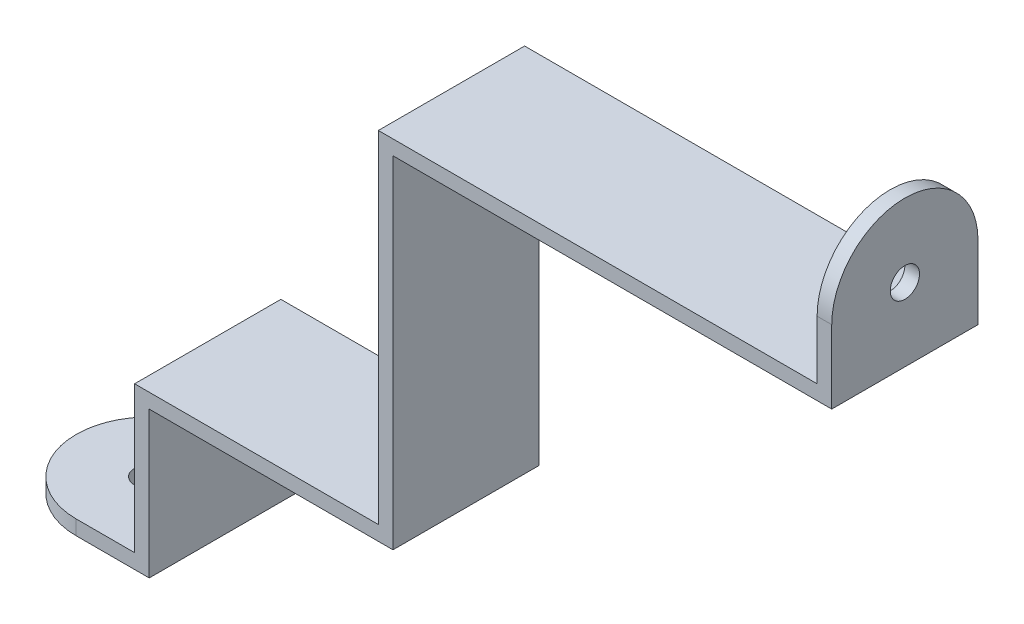
SolidWorks part; units mm, degrees
ref_plane "Front Plane" through (0, 0, 0) normal (0, 0, 1) x (1, 0, 0)
ref_plane "Top Plane" through (0, 0, 0) normal (0, 1, 0) x (1, 0, 0)
ref_plane "Right Plane" through (0, 0, 0) normal (1, 0, 0) x (0, 0, -1)
sketch "Sketch1" plane through (0, 0, 0) normal (0, 0, 1) x (1, 0, 0)
  line L0 (0, 0) -> (0, 35)
  line L3 (-1.5, 36.5) -> (-1.5, 35)
  line L4 (-1.5, 35) -> (-1.5, 1.5)
  line L5 (-1.5, 1.5) -> (-16.5, 1.5)
  line L6 (0, 35) -> (45, 35)
  line L7 (45, 35) -> (45, 50)
  line L8 (45, 50) -> (43.5, 50)
  line L9 (0, 0) -> (-25, 0)
  line L10 (-25, 0) -> (-25, -15)
  line L11 (-25, -15) -> (-40, -15)
  line L12 (-40, -15) -> (-40, -13.5)
  line L13 (-40, -13.5) -> (-26.5, -13.5)
  line L14 (-26.5, -13.5) -> (-26.5, 1.5)
  line L15 (-26.5, 1.5) -> (-16.5, 1.5)
  line L16 (43.5, 50) -> (43.5, 36.5)
  line L17 (43.5, 36.5) -> (-1.5, 36.5)
extrude "Boss-Extrude1" add sketch "Sketch1" along normal blind 15
sketch "Sketch5" plane through (43.5, 0, 0) normal (-1, 0, 0) x (0, 0, 1)
  line L0 (7.5, 50) -> (7.5, 42.5) construction
  line L1 (15, 50) -> (0, 50) construction
  line L2 (0, 42.5) -> (0, 50)
  line L3 (0, 50) -> (15, 50)
  line L4 (15, 50) -> (15, 42.5)
  circle A0 centre (7.5, 42.5) radius 1.5
  arc A1 (15, 42.5) -> (0, 42.5) centre (7.5, 42.5) ccw
  line M1 (0, 50) -> (0, 36.5)
  line M3 (15, 36.5) -> (15, 50)
  line M4 (15, 50) -> (0, 50)
extrude "Cut-Extrude3" cut sketch "Sketch5" against normal blind 10 contours A0 | A1 L3 M1 | A1 M3 M4 region at (43.5, 48.3247, 13.3247) region at (43.5, 48.3247, 1.6753) region at (43.5, 42.5, 7.5)
sketch "Sketch6" plane through (0, -13.5, 0) normal (0, 1, 0) x (1, 0, 0)
  line L0 (-40, -7.5) -> (-32.5, -7.5) construction
  line L1 (-40, -15) -> (-40, 0) construction
  line L2 (-32.5, -15) -> (-40, -15)
  line L3 (-40, -15) -> (-40, 0)
  line L4 (-40, 0) -> (-32.5, 0)
  circle A0 centre (-32.5, -7.5) radius 1.5
  arc A1 (-32.5, 0) -> (-32.5, -15) centre (-32.5, -7.5) ccw
  line M1 (-26.5, 0) -> (-40, 0)
  line M2 (-40, 0) -> (-40, -15)
  line M3 (-40, -15) -> (-26.5, -15)
extrude "Cut-Extrude4" cut sketch "Sketch6" against normal blind 10 contours A1 M1 M2 | A0 | A1 L3 M3 region at (-38.3247, -13.5, 1.6753) region at (-38.3247, -13.5, 13.3247) region at (-32.5, -13.5, 7.5)
